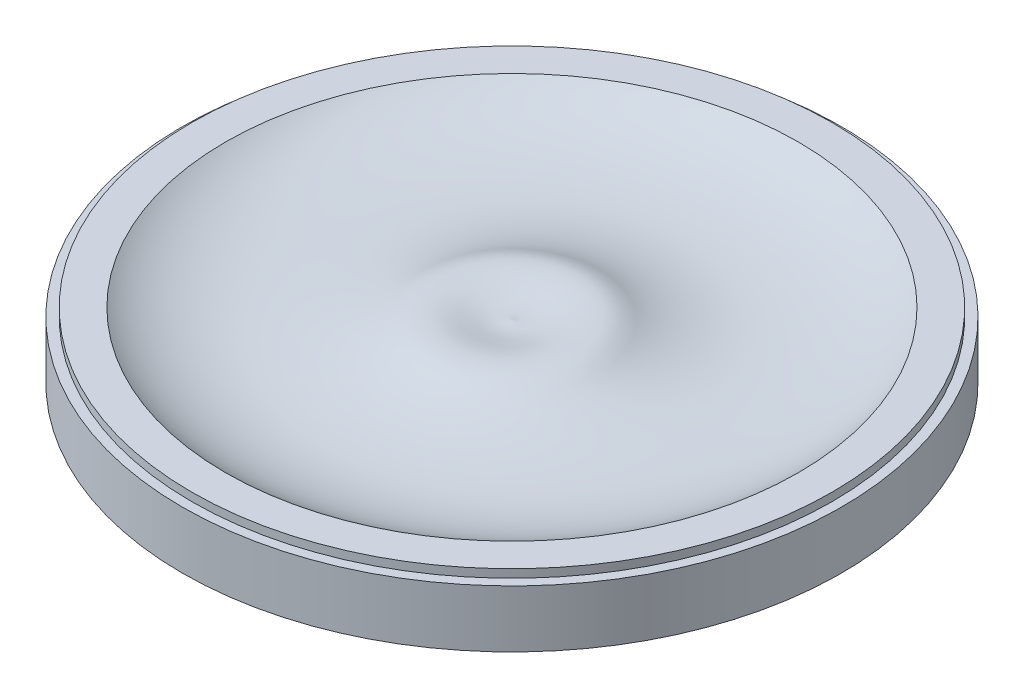
SolidWorks part; units mm, degrees
ref_plane "Front Plane" through (0, 0, 0) normal (0, 0, 1) x (1, 0, 0)
ref_plane "Top Plane" through (0, 0, 0) normal (0, 1, 0) x (1, 0, 0)
ref_plane "Right Plane" through (0, 0, 0) normal (1, 0, 0) x (0, 0, -1)
sketch "Sketch1" plane through (0, 0, 0) normal (1, 0, 0) x (0, 0, -1)
  line L0 (0, 2.675) -> (0, -2.675)
  line L1 (0, 2.675) -> (13.6, 2.675)
  line L2 (13.6, 2.675) -> (13.6, 2.325)
  line L3 (13.6, 2.325) -> (14, 2.325)
  line L4 (14, 2.325) -> (14, -0.105)
  line L5 (14, -0.105) -> (12.5, -0.105)
  line L6 (12.5, -0.105) -> (12.5, -1.105)
  line L7 (12.5, -1.105) -> (6.65, -1.105)
  line L8 (6.65, -1.105) -> (6.65, -2.675)
  line L9 (6.65, -2.675) -> (0, -2.675)
  point P3 (0, -2.675)
  point P14 (13.6, 2.675)
  point P15 (0, -2.5368)
  point P16 (13.6, 2.325)
  dimension "D1" = 5.35
  dimension "D2" = 0.35
  dimension "D3" = 2.78
  dimension "D4" = 1
  dimension "D5" = 6.65
  dimension "D6" = 14
  dimension "D7" = 0.4
  dimension "D8" = 12.5
revolve "Revolve1" add sketch "Sketch1" angle 360 about L0
sketch "Sketch2" plane through (0, 0, 0) normal (0, 0, 1) x (1, 0, 0)
  line L0 (0, -2.675) -> (0, 2.675) construction
  line L1 (-6.65, -2.675) -> (6.65, -2.675) construction
  line L2 (13.6, 2.675) -> (-13.6, 2.675) construction
  line L3 (13.6, 2.325) -> (-13.6, 2.325) construction
  line L4 (12.1678, 2.675) -> (12.1678, 4.1884)
  line L5 (12.1678, 4.1884) -> (0, 4.1884)
  line L6 (0, 4.1884) -> (0, 2.2093)
  line L7 (14, 2.325) -> (-14, 2.325) construction
  spline S0 degree 3 poles (0, 2.2093) (0.6975, 2.0961) (1.713, 2.4794) (3.0898, 2.5245) (5.5226, 1.2734) (10.1356, 1.1049) (12.1678, 2.675) knots 0 0 0 0 0.198884 0.33463 0.396963 1 1 1 1
  point P8 (4.0118, 2.325)
  point P17 (2.05, 2.675)
  point P20 (1.9559, 2.4297)
  point P21 (3.4468, 2.325)
revolve "Cut-Revolve1" cut sketch "Sketch2" angle 360 about L0
sketch "Sketch3" plane through (0, -1.105, 0) normal (0, -1, 0) x (1, 0, 0)
  line L0 (0, 0) -> (0, -12.5) construction
  line L1 (6.125, -7.2618) -> (8.0592, -9.5551)
  line L2 (-6.125, -7.2618) -> (-8.0592, -9.5551)
  line L3 (6.125, -7.2618) -> (-6.125, -7.2618) construction
  arc A0 (8.0592, -9.5551) -> (-8.0592, -9.5551) centre (0, 0) cw
  circle A1 centre (0, 0) radius 12.5 construction
  arc A2 (6.125, -7.2618) -> (-6.125, -7.2618) centre (0, 0) cw
  circle A3 centre (0, 0) radius 12.5 construction
  dimension "D1" = 12.25
  dimension "D2" = 3
extrude "Boss-Extrude1" add sketch "Sketch3" along normal blind 0.75
sketch "Sketch4" plane through (0, -1.855, 0) normal (0, -1, 0) x (1, 0, 0)
  line L0 (0, 0) -> (0, -10.4322) construction
  ellipse E0 centre (6.1689, -8.9403) end of major axis (6.9149, -10.0095) minor radius 0.9053
  ellipse E1 centre (-6.1689, -8.9403) end of major axis (-6.9149, -10.0095) minor radius 0.9053
extrude "Boss-Extrude2" add sketch "Sketch4" along normal blind 0.1
fillet "Fillet1" radius 0.1 2 edges at (-6.9149, -1.955, -10.0095) (6.9149, -1.955, -10.0095)
